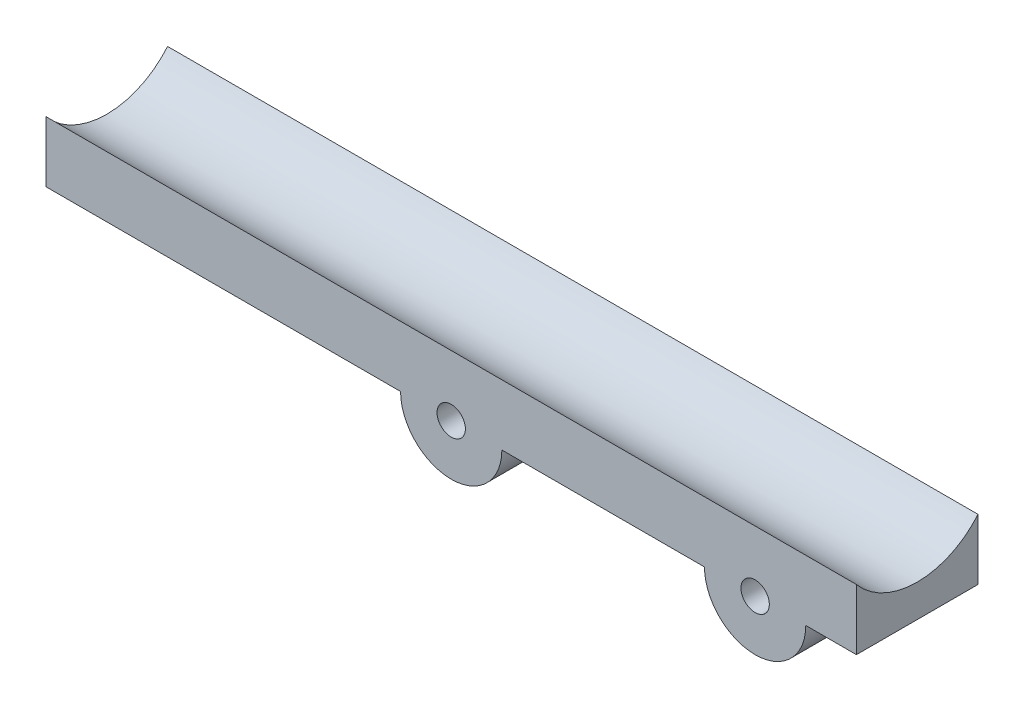
SolidWorks part; units mm, degrees
ref_plane "Front Plane" through (0, 0, 0) normal (0, 0, 1) x (1, 0, 0)
ref_plane "Top Plane" through (0, 0, 0) normal (0, 1, 0) x (1, 0, 0)
ref_plane "Right Plane" through (0, 0, 0) normal (1, 0, 0) x (0, 0, -1)
sketch "Sketch1" plane through (0, 0, 0) normal (0, 0, 1) x (1, 0, 0)
  line L0 (87.5, 0) -> (112.5, 0)
  line L1 (0, 0) -> (200, 0)
  line L2 (0, 0) -> (0, 15)
  line L3 (0, 15) -> (200, 15)
  line L4 (200, 0) -> (200, 15)
  line L5 (100, 0) -> (175, 0)
  circle A0 centre (100, 0) radius 12.5
  circle A1 centre (175, 0) radius 12.5
  point P8 (100, 0)
  dimension "D4" = 75
  dimension "D5" = 25
  dimension "D1" = 15
  dimension "D2" = 200
  dimension "D3" = 25
extrude "Boss-Extrude1" add sketch "Sketch1" along normal blind 30 contours A1 L4 L3 L2 L1 A0 | L1 A1 L5 | L5 A1 L1 | L0 A0 L1 | L1 A0 L0 region at (100, 5.3052, 0) region at (43.75, 2.0056, 0) region at (100, -5.3052, 0) region at (175, 5.3052, 0) region at (175, -5.3052, 0)
sketch "Sketch2" plane through (0, 0, 30) normal (0, 0, 1) x (1, 0, 0)
  line L5 (112.5, 0) -> (162.5, 0)
  line L6 (200, 0) -> (200, 15)
  line L7 (200, 15) -> (0, 15)
  line L8 (0, 15) -> (0, 0)
  line L9 (0, 0) -> (87.5, 0)
  line L10 (112.5, 0) -> (162.5, 0) construction
  line L11 (200, 0) -> (200, 15) construction
  line L12 (200, 15) -> (0, 15) construction
  line L13 (0, 15) -> (0, 0) construction
  line L14 (0, 0) -> (87.5, 0) construction
  line L16 (187.5, 0) -> (200, 0)
  line L17 (187.5, 0) -> (200, 0)
  circle A0 centre (100, 0) radius 3.5
  circle A1 centre (175, 0) radius 3.5
  arc A2 (162.5, 0) -> (187.5, 0) centre (175, 0) ccw
  arc A3 (87.5, 0) -> (112.5, 0) centre (100, 0) ccw
  arc A4 (162.5, 0) -> (187.5, 0) centre (175, 0) ccw construction
  arc A5 (87.5, 0) -> (112.5, 0) centre (100, 0) ccw construction
  circle A6 centre (100, 0) radius 8
  circle A7 centre (100, 0) radius 9.5
  circle A8 centre (175, 0) radius 8
  circle A9 centre (175, 0) radius 9.5
  dimension "D2" = 7
  dimension "D3" = 7
  dimension "D4" = 16
  dimension "D5" = 19
  dimension "D6" = 16
  dimension "D7" = 19
  dimension "D1" = 0
extrude "Cut-Extrude2" cut sketch "Sketch2" against normal up to next contours A0 | A1 region at (100, 0, 30) region at (175, 0, 30)
extrude "Cut-Extrude3" cut sketch "Sketch2<3>" along normal offset from surface (3 mm away) 27 from surface contours A6 A0 | A8 A1 region at (92.2263, 0, 30) region at (167.2263, 0, 30) up to face at (103.5, 0, 30) starting at face at (103.5, 0, 0)
sketch "Sketch2<3>" plane through (0, 0, 30) normal (0, 0, 1) x (1, 0, 0) same geometry as "Sketch2"
ref_plane "Plane1" through (0, 0, 15) normal (0, 0, 1) x (1, 0, 0)
sketch "Sketch3" plane through (0, 0, 0) normal (-1, 0, 0) x (0, 0, 1)
  line L0 (0, 15) -> (30, 15)
  arc A0 (0, 15) -> (30, 15) centre (15, 27.5714) ccw
  point P4 (15, 15)
  point P7 (15, 8)
  dimension "D1" = 7
extrude "Cut-Extrude4" cut sketch "Sketch3" against normal up to next
